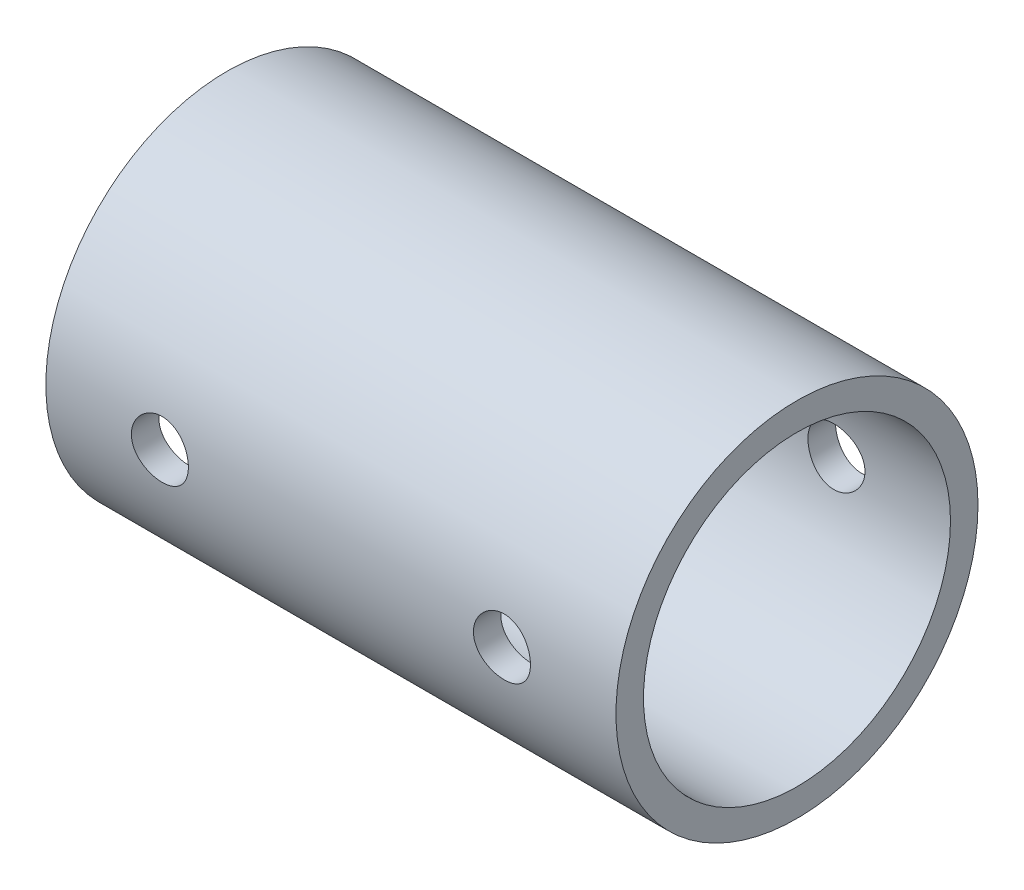
SolidWorks part; units mm, degrees
ref_plane "Front Plane" through (0, 0, 0) normal (0, 0, 1) x (1, 0, 0)
ref_plane "Top Plane" through (0, 0, 0) normal (0, 1, 0) x (1, 0, 0)
ref_plane "Right Plane" through (0, 0, 0) normal (1, 0, 0) x (0, 0, -1)
sketch "Sketch1" plane through (0, 0, 0) normal (1, 0, 0) x (0, 0, -1)
  circle A0 centre (0, 0) radius 15.875
  circle A1 centre (0, 0) radius 13.462
  dimension "D1" = 31.75
  dimension "D2" = 2.413
extrude "Boss-Extrude1" add sketch "Sketch1" along normal blind 25 and the other way blind 25
sketch "Sketch2" plane through (0, 0, 0) normal (0, 0, 1) x (1, 0, 0)
  line L0 (-25, 0) -> (0, 0) construction
  line L1 (-25, 15.875) -> (-25, -15.875) construction
  line L2 (0, 0) -> (25, 0) construction
  line L3 (25, -15.875) -> (25, 15.875) construction
  circle A0 centre (-15, 0) radius 2.5
  circle A1 centre (15, 0) radius 2.5
  dimension "D2" = 5
  dimension "D1" = 10
  dimension "D3" = 10
extrude "Cut-Extrude1" cut sketch "Sketch2" against normal blind 25 and the other way blind 25
